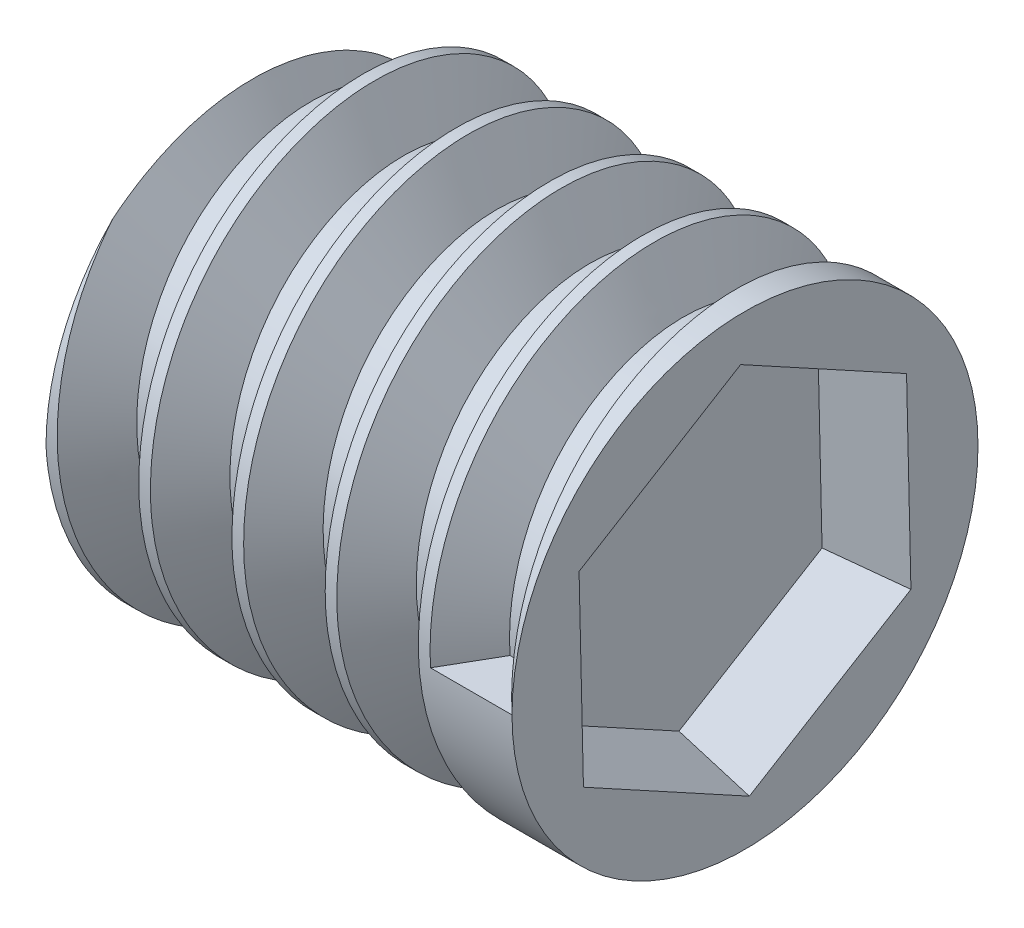
SolidWorks part; units mm, degrees
ref_plane "Front Plane" through (0, 0, 0) normal (1, 0, 0) x (0, 1, 0)
ref_plane "Top Plane" through (0, 0, 0) normal (0, 0, 1) x (0, 1, 0)
ref_plane "Right Plane" through (0, 0, 0) normal (0, 1, 0) x (-1, 0, 0)
sketch "Sketch1" plane through (0, 0, 0) normal (1, 0, 0) x (0, 1, 0)
  circle A0 centre (0, 0) radius 1
  dimension "D1" = 2
extrude "Boss-Extrude1" add sketch "Sketch1" along normal blind 2
thread "Thread1" pitch 0.4 method cut profile "Thread Profile1" start angle 0, offset 0, length 2, pitch 0.4, diameter 2
ref_plane "Plane1" through (2, 0, 1) normal (0, -1, 0) x (0, 0, 1)
sketch "Thread Profile1" plane through (2, 0, 1) normal (0, -1, 0) x (0, 0, 1)
  line L0 (0, 0) -> (0, 0.4) construction
  line L11 (0, 0) -> (0, 0.35)
  line L12 (0, 0.35) -> (-0.2165, 0.225)
  line L13 (-0.2165, 0.225) -> (-0.2165, 0.125)
  line L15 (-0.2165, 0.125) -> (0, 0)
  line L17 (-0.2165, 0.175) -> (0, 0.175) construction
  point P2 (0, 0)
  dimension "Pitch" = 0.4
  dimension "Profile_Angle" = 60
  dimension "Profile_Land" = 0.1
  dimension "Profile_Height" = 0.2165
sketch "Sketch4" plane through (2, 0, 0) normal (1, 0, 0) x (0, 1, 0)
  line L1 (-0.3895, -0.7121) -> (0.422, -0.6934)
  line L2 (0.422, -0.6934) -> (0.8115, 0.0188)
  line L3 (0.8115, 0.0188) -> (0.3895, 0.7121)
  line L4 (0.3895, 0.7121) -> (-0.422, 0.6934)
  line L5 (-0.422, 0.6934) -> (-0.8115, -0.0188)
  line L6 (-0.8115, -0.0188) -> (-0.3895, -0.7121)
  circle A0 centre (0, 0) radius 0.7029 construction
  point P1 (0.3623, -0.586)
  point P10 (0.422, -0.6934)
extrude "Cut-Extrude1" cut sketch "Sketch4" against normal blind 0.3 draft 15
